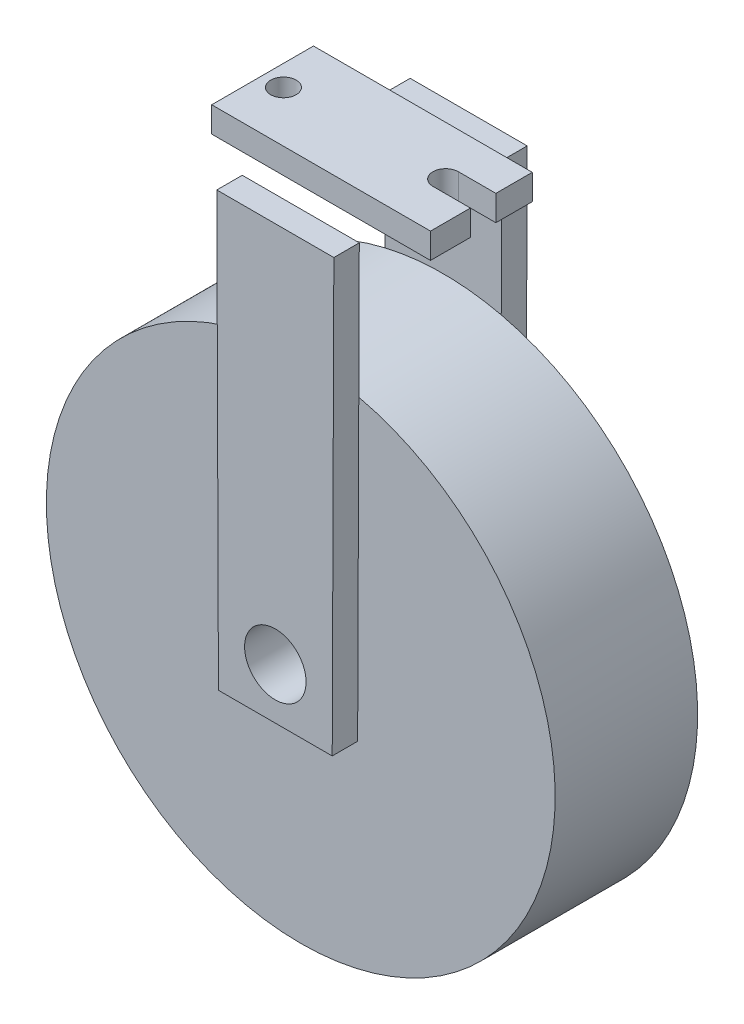
SolidWorks part; units mm, degrees
ref_plane "Спереди" through (0, 0, 0) normal (0, 0, 1) x (1, 0, 0)
ref_plane "Сверху" through (0, 0, 0) normal (0, 1, 0) x (1, 0, 0)
ref_plane "Справа" through (0, 0, 0) normal (1, 0, 0) x (0, 0, -1)
sketch "Эскиз1" plane through (0, 0, 0) normal (0, 1, 0) x (1, 0, 0)
  line L0 (14.1292, 2.8436) -> (21.5, 2.8436)
  line L1 (-21.5, -10) -> (21.5, -10)
  line L2 (-21.5, -10) -> (-21.5, 10)
  line L3 (-21.5, 10) -> (21.5, 10)
  line L4 (21.5, -10) -> (21.5, -2.1564)
  line L5 (-21.5, -10) -> (21.5, 10) construction
  line L6 (-21.5, 10) -> (21.5, -10) construction
  line L7 (14.1292, -2.1564) -> (21.5, -2.1564)
  line L8 (21.5, 2.8436) -> (21.5, 10)
  circle A4 centre (-17.4061, 0) radius 2.5
  arc A5 (14.1292, 2.8436) -> (14.1292, -2.1564) centre (14.1292, 0.3436) ccw
  point P0 (0, 0)
  dimension "D3" = 2.5
  dimension "D4" = 5
  dimension "D1" = 43
  dimension "D2" = 20
extrude "Бобышка-Вытянуть1" add sketch "Эскиз1" along normal blind 5
sketch "Эскиз2" plane through (0, 0, 0) normal (0, 0, 1) x (1, 0, 0)
  line L2 (-46.046, -125) -> (131.9496, -125) construction
  line L3 (-21.5, 5) -> (21.5, 5) construction
  circle A0 centre (0, -75) radius 50
  dimension "D1" = 100
  dimension "D3" = 130
extrude "Бобышка-Вытянуть2" add sketch "Эскиз2" along normal blind 28 from offset 14 separate body offset against normal yes
sketch "Эскиз3" plane through (0, 0, 14) normal (0, 0, 1) x (1, 0, 0)
  line L0 (-11.1803, -85) -> (11.1803, -85)
  line L1 (11.1803, -85) -> (11.5, 0)
  line L2 (-21.5, 0) -> (21.5, 0) construction
  line L3 (11.5, 0) -> (-11.5, 0)
  line L4 (-11.5, 0) -> (-11.1803, -85)
  line L5 (-50, -75) -> (50, -75) construction
  circle A0 centre (0, -75) radius 50 construction
  point P13 (0, -75)
  dimension "D1" = 10
  dimension "D2" = 10
  dimension "D3" = 10
  dimension "D4" = 15
  dimension "D5" = 15
extrude "Бобышка-Вытянуть3" add sketch "Эскиз3" along normal blind 5
pattern_linear "Линейный массив1" count 2 spacing 33 along (0, 0, -1) of "Бобышка-Вытянуть3"
sketch "Эскиз4" plane through (0, 0, -19) normal (0, 0, -1) x (-1, 0, 0)
  circle A0 centre (0, -75) radius 6.0449
extrude "Вырез-Вытянуть1" cut sketch "Эскиз4" against normal through all
